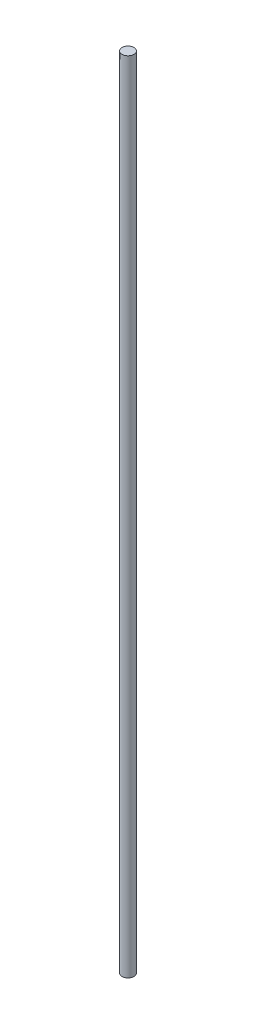
SolidWorks part; units mm, degrees
material "Stainless Steel (ferritic)"
ref_plane "Front Plane" through (0, 0, 0) normal (0, 0, 1) x (1, 0, 0)
ref_plane "Top Plane" through (0, 0, 0) normal (0, 1, 0) x (1, 0, 0)
ref_plane "Right Plane" through (0, 0, 0) normal (1, 0, 0) x (0, 0, -1)
sketch "Sketch1" plane through (0, 0, 0) normal (0, 1, 0) x (1, 0, 0)
  circle A0 centre (0, 0) radius 3
  dimension "D1" = 6
extrude "Boss-Extrude1" add sketch "Sketch1" along normal blind 400
